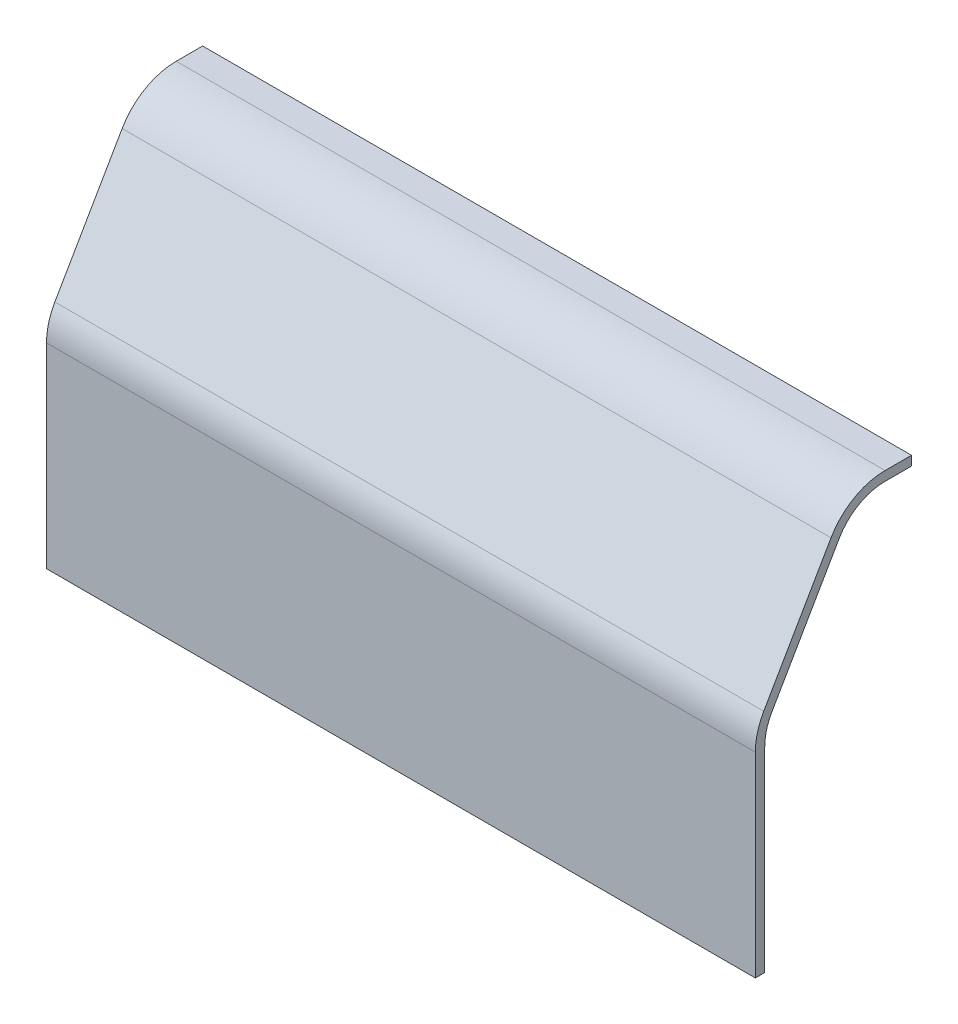
SolidWorks part; units mm, degrees
ref_plane "Alzado" through (0, 0, 0) normal (0, 0, 1) x (1, 0, 0)
ref_plane "Planta" through (0, 0, 0) normal (0, 1, 0) x (1, 0, 0)
ref_plane "Vista lateral" through (0, 0, 0) normal (1, 0, 0) x (0, 0, -1)
sketch "Croquis1" plane through (0, 0, 0) normal (1, 0, 0) x (0, 0, -1)
  line L0 (0, 0) -> (0, 67.1962)
  line L1 (0, 67.1962) -> (28.7321, 116.9615)
  line L2 (28.7321, 116.9615) -> (47, 116.9615)
  line L3 (47, 116.9615) -> (47, 119.9615)
  line L4 (47, 119.9615) -> (27, 119.9615)
  line L5 (27, 119.9615) -> (-3, 68)
  line L6 (-3, 68) -> (-3, 0)
  line L7 (-3, 0) -> (0, 0)
  line L8 (0, 67.1962) -> (29.2398, 67.1962) construction
  dimension "D1" = 3
  dimension "D2" = 3
  dimension "D3" = 3
  dimension "D4" = 68
  dimension "D5" = 60
  dimension "D6" = 20
  dimension "D7" = 60
extrude "Saliente-Extruir1" add sketch "Croquis1" along normal mid plane 227
fillet "Redondeo1" radius 20 1 edges at (0, 68, 3)
fillet "Redondeo2" radius 20 1 edges at (0, 119.9615, -27)
fillet "Redondeo3" radius 17 1 edges at (0, 116.9615, -28.7321)
fillet "Redondeo4" radius 17 1 edges at (0, 67.1962, 0)
